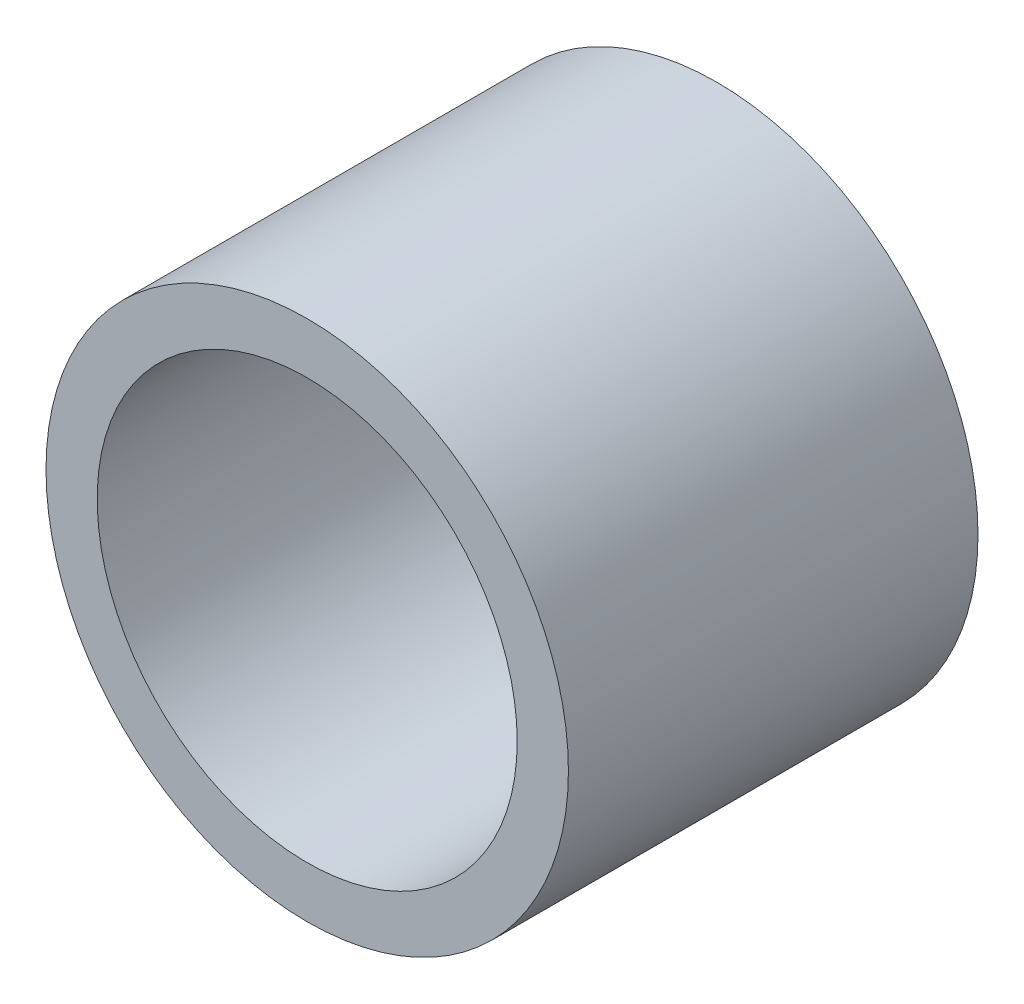
SolidWorks part; units mm, degrees
ref_plane "Front Plane" through (0, 0, 0) normal (0, 0, 1) x (1, 0, 0)
ref_plane "Top Plane" through (0, 0, 0) normal (0, 1, 0) x (1, 0, 0)
ref_plane "Right Plane" through (0, 0, 0) normal (1, 0, 0) x (0, 0, -1)
sketch "Sketch1" plane through (0, 0, 0) normal (0, 0, 1) x (1, 0, 0)
  line L0 (6.35, 0) -> (-6.35, 0) construction
  line L1 (0, -5.1054) -> (0, 5.1054) construction
  line L2 (0, -6.35) -> (0, 6.35) construction
  circle A0 centre (0, 0) radius 6.35 construction
  circle A1 centre (0, 0) radius 5.1054 construction
  point P6 (0, 0)
  point P7 (-5.1054, 0)
  point P8 (5.1054, 0)
  point P10 (-6.35, 0)
  point P11 (6.35, 0)
  point P14 (0, 0)
  point P17 (0, 0)
  point P18 (0, 5.1054)
  point P19 (0, 6.35)
  point P20 (0, -5.1054)
  point P21 (0, -6.35)
  dimension "OD" = 12.7
  dimension "ID" = 10.2108
  dimension "Wall Thickness" = 1.2446
sketch "Sketch2" plane through (0, 0, 0) normal (1, 0, 0) x (0, 0, -1)
  line L0 (0, -5.1054) -> (0, 5.1054) construction
  line L1 (0, -5.1054) -> (0, 5.1054) construction
  line L2 (0, -6.35) -> (0, 6.35) construction
  line L3 (0, -6.35) -> (0, 6.35) construction
  line L4 (4.9784, 6.35) -> (-4.9784, 6.35) construction
  line L5 (4.9784, 5.1054) -> (-4.9784, 5.1054) construction
  line L6 (4.9784, -5.1054) -> (-4.9784, -5.1054) construction
  line L7 (4.9784, -6.35) -> (-4.9784, -6.35) construction
  line L8 (-4.9784, -6.35) -> (-4.9784, 6.35) construction
  line L9 (4.9784, 6.35) -> (4.9784, -6.35) construction
  line L10 (4.9784, 0) -> (-4.9784, 0) construction
  line L11 (0.666, -6.35) -> (0.666, 6.35) construction
  line L12 (-0.666, -6.35) -> (-0.666, 6.35) construction
  point P7 (0, 6.35)
  point P10 (0, 5.1054)
  point P13 (0, -5.1054)
  point P16 (0, -6.35)
  point P17 (-4.9784, -6.35)
  point P18 (-4.9784, -5.1054)
  point P19 (-4.9784, 5.1054)
  point P20 (-4.9784, 6.35)
  point P21 (4.9784, 6.35)
  point P22 (4.9784, 5.1054)
  point P23 (4.9784, -5.1054)
  point P24 (4.9784, -6.35)
  point P28 (0, 0)
  point P30 (0.666, 0)
  point P31 (0.666, -6.35)
  point P32 (0.666, 6.35)
  point P35 (-0.666, 0)
  point P36 (-0.666, 6.35)
  point P37 (-0.666, -6.35)
  dimension "Length" = 9.9568
  dimension "Break Line" = 5.6444
sketch "Sketch3" plane through (0, 0, 0) normal (0, 0, 1) x (1, 0, 0)
  circle A0 centre (0, 0) radius 5.1054 construction
  circle A1 centre (0, 0) radius 6.35 construction
  circle A2 centre (0, 0) radius 5.1054
  circle A3 centre (0, 0) radius 6.35
extrude "Boss-Extrude1" add sketch "Sketch3" along normal up to vertex (4.9784 mm away) and the other way up to vertex (4.9784 mm away) up to point (0, 0, 4.9784) other way up to point (0, 0, -4.9784)
equation "\"Break Line@Sketch2\"=\"OD@Sketch1\"/2.25"
